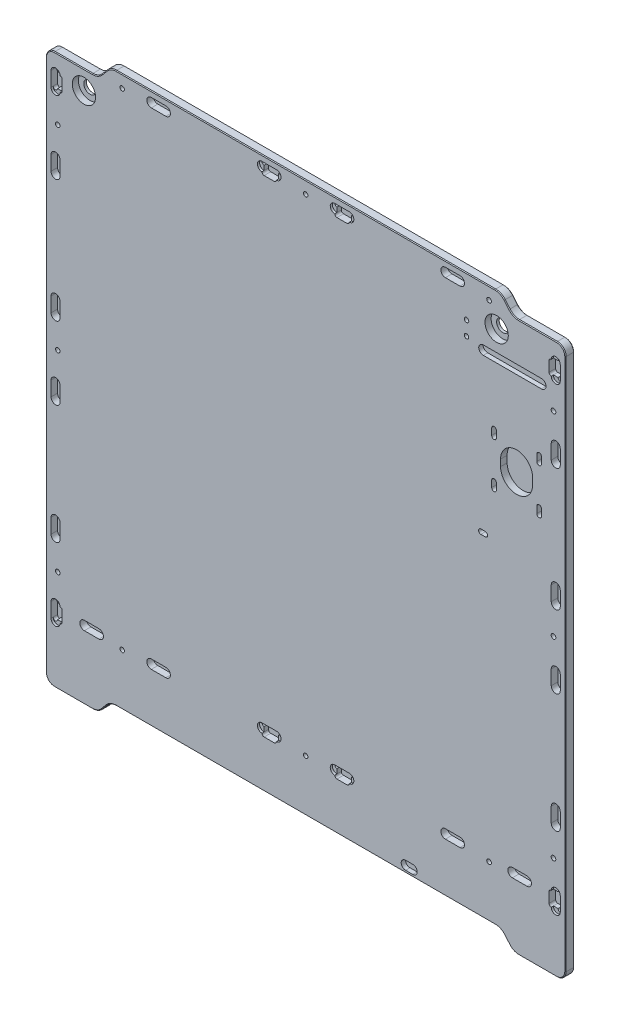
SolidWorks part; units mm, degrees
ref_plane "Alzado" through (0, 0, 0) normal (0, 0, 1) x (1, 0, 0)
ref_plane "Planta" through (0, 0, 0) normal (0, 1, 0) x (1, 0, 0)
ref_plane "Vista lateral" through (0, 0, 0) normal (1, 0, 0) x (0, 0, -1)
ref_plane "Plano1" through (0, 0, 3) normal (0, 0, 1) x (1, 0, 0)
sketch "Croquis1" plane through (0, 0, 3) normal (0, 0, 1) x (1, 0, 0)
  line L0 (178.5, -194) -> (178.5, 194)
  line L1 (178.5, 194) -> (-178.5, 194)
  line L2 (-178.5, 194) -> (-178.5, -194)
  line L3 (-178.5, -194) -> (178.5, -194)
  dimension "D1" = 357
  dimension "D2" = 388
extrude "Saliente-Extruir1" add sketch "Croquis1" against normal blind 6
sketch "Croquis2" plane through (0, 0, 3) normal (0, 0, 1) x (1, 0, 0)
  line L0 (-167.2, -144.2) -> (-168.7, -144.2)
  line L1 (-174.9, -144.2) -> (-174.9, -154.2)
  line L2 (-168.7, -154.2) -> (-167.2, -154.2)
  line L3 (-167.2, -154.2) -> (-167.2, -144.2)
  line L4 (178.5, -194) -> (178.5, 194) construction
  arc A0 (-168.7, -144.2) -> (-174.9, -144.2) centre (-171.8, -144.2) ccw
  arc A1 (-174.9, -154.2) -> (-168.7, -154.2) centre (-171.8, -154.2) ccw
  dimension "D1" = 3.1
  dimension "D2" = 345.7
extrude "Cortar-Extruir1" cut sketch "Croquis2" against normal blind 1.5
sketch "Croquis3" plane through (0, 0, 1.5) normal (0, 0, 1) x (1, 0, 0)
  line L0 (-171.9, -154.2) -> (-167.2, -154.2)
  line L1 (-167.2, -154.2) -> (-167.2, -144.2)
  line L2 (-167.2, -144.2) -> (-171.9, -144.2)
  line L3 (-174.9, -144.2) -> (-174.9, -154.2)
  line L4 (-167.2, -154.2) -> (-167.2, -144.2) construction
  arc A0 (-171.9, -144.2) -> (-174.9, -144.2) centre (-173.4, -144.2) ccw
  arc A1 (-174.9, -154.2) -> (-171.9, -154.2) centre (-173.4, -154.2) ccw
  dimension "D1" = 1.5
  dimension "D2" = 6.2
extrude "Cortar-Extruir2" cut sketch "Croquis3" against normal blind 3
sketch "Croquis4" plane through (0, 0, 3) normal (0, 0, 1) x (1, 0, 0)
  line L0 (-20, 182.4) -> (-20, 183.9)
  line L1 (-20, 190.1) -> (-30, 190.1)
  line L2 (-30, 183.9) -> (-30, 182.4)
  line L3 (-30, 182.4) -> (-20, 182.4)
  line L4 (-167.2, -154.2) -> (-167.2, -144.2) construction
  arc A0 (-20, 183.9) -> (-20, 190.1) centre (-20, 187) ccw
  arc A1 (-30, 190.1) -> (-30, 183.9) centre (-30, 187) ccw
  dimension "D1" = 3.1
  dimension "D2" = 3.1
  dimension "D3" = 137.2
extrude "Cortar-Extruir3" cut sketch "Croquis4" against normal blind 1.5
sketch "Croquis5" plane through (0, 0, 1.5) normal (0, 0, 1) x (1, 0, 0)
  line L0 (-20, 190.1) -> (-30, 190.1)
  line L1 (-30, 187.1) -> (-30, 182.4)
  line L2 (-30, 182.4) -> (-20, 182.4)
  line L3 (-20, 182.4) -> (-20, 187.1)
  arc A0 (-20, 187.1) -> (-20, 190.1) centre (-20, 188.6) ccw
  arc A1 (-30, 190.1) -> (-30, 187.1) centre (-30, 188.6) ccw
  dimension "D1" = 1.5
  dimension "D2" = 1.5
extrude "Cortar-Extruir4" cut sketch "Croquis5" against normal blind 3
sketch "Croquis6" plane through (0, 0, 3) normal (0, 0, 1) x (1, 0, 0)
  line L0 (-167.2, 171.7) -> (-168.7, 171.7)
  line L1 (-174.9, 171.7) -> (-174.9, 161.7)
  line L2 (-168.7, 161.7) -> (-167.2, 161.7)
  line L3 (-167.2, 161.7) -> (-167.2, 171.7)
  line L4 (-20, 182.4) -> (-20, 183.9) construction
  line L5 (-168.7, -154.2) -> (-167.2, -154.2) construction
  arc A0 (-168.7, 171.7) -> (-174.9, 171.7) centre (-171.8, 171.7) ccw
  arc A1 (-174.9, 161.7) -> (-168.7, 161.7) centre (-171.8, 161.7) ccw
  dimension "D1" = 3.1
  dimension "D2" = 147.2
  dimension "D3" = 151.8
  dimension "D4" = 315.9
  dimension "D5" = 325.9
extrude "Cortar-Extruir5" cut sketch "Croquis6" against normal blind 1.5
sketch "Croquis7" plane through (0, 0, 1.5) normal (0, 0, 1) x (1, 0, 0)
  line L0 (-171.9, 161.7) -> (-167.2, 161.7)
  line L1 (-167.2, 161.7) -> (-167.2, 171.7)
  line L2 (-167.2, 171.7) -> (-171.9, 171.7)
  line L3 (-174.9, 171.7) -> (-174.9, 161.7)
  line L4 (-167.2, 161.7) -> (-167.2, 171.7) construction
  arc A0 (-171.9, 171.7) -> (-174.9, 171.7) centre (-173.4, 171.7) ccw
  arc A1 (-174.9, 161.7) -> (-171.9, 161.7) centre (-173.4, 161.7) ccw
  dimension "D1" = 1.5
  dimension "D2" = 6.2
extrude "Cortar-Extruir6" cut sketch "Croquis7" against normal blind 3
sketch "Croquis8" plane through (0, 0, 3) normal (0, 0, 1) x (1, 0, 0)
  line L0 (-20, -151.6) -> (-20, -150.1)
  line L1 (-20, -143.9) -> (-30, -143.9)
  line L2 (-30, -150.1) -> (-30, -151.6)
  line L3 (-30, -151.6) -> (-20, -151.6)
  line L5 (-168.7, 161.7) -> (-167.2, 161.7) construction
  arc A0 (-20, -150.1) -> (-20, -143.9) centre (-20, -147) ccw
  arc A1 (-30, -143.9) -> (-30, -150.1) centre (-30, -147) ccw
  dimension "D1" = 3.1
  dimension "D2" = 308.7
  dimension "D3" = 313.3
extrude "Cortar-Extruir7" cut sketch "Croquis8" against normal blind 1.5
sketch "Croquis9" plane through (0, 0, 1.5) normal (0, 0, 1) x (1, 0, 0)
  line L0 (-30, -146.9) -> (-30, -151.6)
  line L1 (-30, -151.6) -> (-20, -151.6)
  line L2 (-20, -151.6) -> (-20, -146.9)
  line L3 (-20, -143.9) -> (-30, -143.9)
  line L4 (-20, -151.6) -> (-20, -150.1) construction
  arc A0 (-30, -143.9) -> (-30, -146.9) centre (-30, -145.4) ccw
  arc A1 (-20, -146.9) -> (-20, -143.9) centre (-20, -145.4) ccw
  dimension "D1" = 1.5
  dimension "D2" = 10
extrude "Cortar-Extruir8" cut sketch "Croquis9" against normal blind 3
sketch "Croquis10" plane through (0, 0, -3) normal (0, 0, -1) x (-1, 0, 0)
  line L0 (134.1086, 194) -> (134.1086, 183.9996)
  line L1 (134.1086, 183.9996) -> (178.5, 183.9996)
  line L2 (178.5, 183.9996) -> (178.5, 194)
  line L3 (178.5, 194) -> (134.1086, 194)
  line L4 (178.5, 194) -> (178.5, -194) construction
  line L5 (178.5, -194) -> (-178.5, -194) construction
  dimension "D1" = 44.3914
  dimension "D2" = 377.9996
  dimension "D3" = 388
extrude "Cortar-Extruir9" cut sketch "Croquis10" against normal through all
sketch "Croquis11" plane through (0, 0, -3) normal (0, 0, -1) x (-1, 0, 0)
  line L0 (134.1086, -194) -> (134.1086, -183.9996)
  line L1 (134.1086, -183.9996) -> (-134.1086, -183.9996)
  line L2 (-134.1086, -183.9996) -> (-134.1086, -194)
  line L3 (-134.1086, -194) -> (134.1086, -194)
  line L4 (178.5, 183.9996) -> (178.5, -194) construction
  line L5 (134.1086, 183.9996) -> (178.5, 183.9996) construction
  dimension "D1" = 44.3914
  dimension "D2" = 312.6086
  dimension "D3" = 367.9992
  dimension "D4" = 377.9996
extrude "Cortar-Extruir10" cut sketch "Croquis11" against normal through all
sketch "Croquis12" plane through (0, 0, 3) normal (0, 0, 1) x (1, 0, 0)
  line L0 (162, 74.95) -> (162, 79.45)
  line L1 (158.8, 79.45) -> (158.8, 74.95)
  line L2 (-178.5, 183.9996) -> (-178.5, -194) construction
  line L3 (-178.5, -194) -> (-134.1086, -194) construction
  arc A0 (162, 79.45) -> (158.8, 79.45) centre (160.4, 79.45) ccw
  arc A1 (158.8, 74.95) -> (162, 74.95) centre (160.4, 74.95) ccw
  dimension "D1" = 1.6
  dimension "D2" = 338.9
  dimension "D3" = 268.95
  dimension "D4" = 273.45
extrude "Cortar-Extruir11" cut sketch "Croquis12" against normal through all
sketch "Croquis13" plane through (0, 0, 3) normal (0, 0, 1) x (1, 0, 0)
  line L0 (158.8, 110.45) -> (158.8, 105.95)
  line L1 (162, 105.95) -> (162, 110.45)
  line L2 (-178.5, 183.9996) -> (-178.5, -194) construction
  line L3 (-178.5, -194) -> (-134.1086, -194) construction
  arc A0 (158.8, 105.95) -> (162, 105.95) centre (160.4, 105.95) ccw
  arc A1 (162, 110.45) -> (158.8, 110.45) centre (160.4, 110.45) ccw
  dimension "D1" = 1.6
  dimension "D2" = 338.9
  dimension "D3" = 299.95
  dimension "D4" = 304.45
extrude "Cortar-Extruir12" cut sketch "Croquis13" against normal through all
sketch "Croquis14" plane through (0, 0, 3) normal (0, 0, 1) x (1, 0, 0)
  line L0 (127.8, 79.45) -> (127.8, 74.95)
  line L1 (131, 74.95) -> (131, 79.45)
  line L2 (-178.5, 183.9996) -> (-178.5, -194) construction
  line L3 (-178.5, -194) -> (-134.1086, -194) construction
  arc A0 (131, 79.45) -> (127.8, 79.45) centre (129.4, 79.45) ccw
  arc A1 (127.8, 74.95) -> (131, 74.95) centre (129.4, 74.95) ccw
  dimension "D1" = 1.6
  dimension "D2" = 307.9
  dimension "D3" = 268.95
  dimension "D4" = 273.45
extrude "Cortar-Extruir13" cut sketch "Croquis14" against normal through all
sketch "Croquis15" plane through (0, 0, 3) normal (0, 0, 1) x (1, 0, 0)
  line L0 (127.8, 110.45) -> (127.8, 105.95)
  line L1 (131, 105.95) -> (131, 110.45)
  line L2 (-178.5, 183.9996) -> (-178.5, -194) construction
  line L3 (-178.5, -194) -> (-134.1086, -194) construction
  arc A0 (131, 110.45) -> (127.8, 110.45) centre (129.4, 110.45) ccw
  arc A1 (127.8, 105.95) -> (131, 105.95) centre (129.4, 105.95) ccw
  dimension "D1" = 1.6
  dimension "D2" = 307.9
  dimension "D3" = 299.95
  dimension "D4" = 304.45
extrude "Cortar-Extruir14" cut sketch "Croquis15" against normal through all
sketch "Croquis16" plane through (0, 0, -3) normal (0, 0, -1) x (-1, 0, 0)
  line L0 (-123.4, 43.4) -> (-120.4, 43.4)
  line L1 (-120.4, 46.6) -> (-123.4, 46.6)
  line L2 (-127.8, 79.45) -> (-127.8, 74.95) construction
  arc A0 (-120.4, 43.4) -> (-120.4, 46.6) centre (-120.4, 45) ccw
  arc A1 (-123.4, 46.6) -> (-123.4, 43.4) centre (-123.4, 45) ccw
  dimension "D1" = 1.6
  dimension "D2" = 4.4
  dimension "D3" = 7.4
  dimension "D4" = 29.95
extrude "Cortar-Extruir15" cut sketch "Croquis16" against normal through all
sketch "Croquis17" plane through (0, 0, 3) normal (0, 0, 1) x (1, 0, 0)
  line L0 (73.65, -176.3) -> (68.65, -176.3)
  line L1 (68.65, -182.3) -> (73.65, -182.3)
  line L2 (178.5, -194) -> (178.5, 194) construction
  line L3 (134.1086, -194) -> (178.5, -194) construction
  arc A0 (68.65, -176.3) -> (68.65, -182.3) centre (68.65, -179.3) ccw
  arc A1 (73.65, -182.3) -> (73.65, -176.3) centre (73.65, -179.3) ccw
  dimension "D1" = 3
  dimension "D2" = 104.85
  dimension "D3" = 109.85
  dimension "D4" = 14.7
extrude "Cortar-Extruir16" cut sketch "Croquis17" against normal blind 3
sketch "Croquis18" plane through (0, 0, 3) normal (0, 0, 1) x (1, 0, 0)
  line L0 (122, 150.7237) -> (162, 150.7237)
  line L1 (162, 156.9237) -> (122, 156.9237)
  line L2 (-134.1086, 183.9996) -> (-134.1086, 194) construction
  line L3 (178.5, 194) -> (-134.1086, 194) construction
  arc A0 (162, 150.7237) -> (162, 156.9237) centre (162, 153.8237) ccw
  arc A1 (122, 156.9237) -> (122, 150.7237) centre (122, 153.8237) ccw
  dimension "D1" = 3.1
  dimension "D2" = 256.1086
  dimension "D3" = 296.1086
  dimension "D4" = 40.1763
extrude "Cortar-Extruir17" cut sketch "Croquis18" against normal blind 3
sketch "Croquis19" plane through (0, 0, 3) normal (0, 0, 1) x (1, 0, 0)
  line L0 (-152, -150.1) -> (-142, -150.1)
  line L1 (-142, -143.9) -> (-152, -143.9)
  line L2 (178.5, -194) -> (178.5, 194) construction
  line L3 (134.1086, -194) -> (178.5, -194) construction
  arc A0 (-142, -150.1) -> (-142, -143.9) centre (-142, -147) ccw
  arc A1 (-152, -143.9) -> (-152, -150.1) centre (-152, -147) ccw
  dimension "D1" = 3.1
  dimension "D2" = 320.5
  dimension "D3" = 330.5
  dimension "D4" = 47
extrude "Cortar-Extruir18" cut sketch "Croquis19" against normal blind 4.5
sketch "Croquis20" plane through (0, 0, 3) normal (0, 0, 1) x (1, 0, 0)
  line L0 (-106, -150.1) -> (-96, -150.1)
  line L1 (-96, -143.9) -> (-106, -143.9)
  line L2 (162, 105.95) -> (162, 110.45) construction
  line L3 (162, 156.9237) -> (122, 156.9237) construction
  arc A0 (-96, -150.1) -> (-96, -143.9) centre (-96, -147) ccw
  arc A1 (-106, -143.9) -> (-106, -150.1) centre (-106, -147) ccw
  dimension "D1" = 3.1
  dimension "D2" = 258
  dimension "D3" = 268
  dimension "D4" = 303.9237
extrude "Cortar-Extruir19" cut sketch "Croquis20" against normal blind 4.5
sketch "Croquis21" plane through (0, 0, 3) normal (0, 0, 1) x (1, 0, 0)
  line L0 (-168.7, -104.2) -> (-168.7, -94.2)
  line L1 (-174.9, -94.2) -> (-174.9, -104.2)
  line L2 (162, 105.95) -> (162, 110.45) construction
  line L3 (68.65, -182.3) -> (73.65, -182.3) construction
  arc A0 (-174.9, -104.2) -> (-168.7, -104.2) centre (-171.8, -104.2) ccw
  arc A1 (-168.7, -94.2) -> (-174.9, -94.2) centre (-171.8, -94.2) ccw
  dimension "D1" = 3.1
  dimension "D2" = 333.8
  dimension "D3" = 78.1
  dimension "D4" = 88.1
extrude "Cortar-Extruir20" cut sketch "Croquis21" against normal blind 4.5
sketch "Croquis22" plane through (0, 0, 3) normal (0, 0, 1) x (1, 0, 0)
  line L0 (-168.7, -22.5) -> (-168.7, -12.5)
  line L1 (-174.9, -12.5) -> (-174.9, -22.5)
  line L2 (-174.9, -94.2) -> (-174.9, -104.2) construction
  line L3 (68.65, -182.3) -> (73.65, -182.3) construction
  arc A0 (-174.9, -22.5) -> (-168.7, -22.5) centre (-171.8, -22.5) ccw
  arc A1 (-168.7, -12.5) -> (-174.9, -12.5) centre (-171.8, -12.5) ccw
  dimension "D1" = 3.1
  dimension "D2" = 3.1
  dimension "D3" = 159.8
  dimension "D4" = 169.8
extrude "Cortar-Extruir21" cut sketch "Croquis22" against normal blind 4.5
sketch "Croquis23" plane through (0, 0, 3) normal (0, 0, 1) x (1, 0, 0)
  line L0 (-168.7, 27.5) -> (-168.7, 37.5)
  line L1 (-174.9, 37.5) -> (-174.9, 27.5)
  line L2 (-174.9, -94.2) -> (-174.9, -104.2) construction
  line L3 (68.65, -182.3) -> (73.65, -182.3) construction
  arc A0 (-174.9, 27.5) -> (-168.7, 27.5) centre (-171.8, 27.5) ccw
  arc A1 (-168.7, 37.5) -> (-174.9, 37.5) centre (-171.8, 37.5) ccw
  dimension "D1" = 3.1
  dimension "D2" = 3.1
  dimension "D3" = 209.8
  dimension "D4" = 219.8
extrude "Cortar-Extruir22" cut sketch "Croquis23" against normal blind 4.5
sketch "Croquis24" plane through (0, 0, 3) normal (0, 0, 1) x (1, 0, 0)
  line L0 (-168.7, 111.7) -> (-168.7, 121.7)
  line L1 (-174.9, 121.7) -> (-174.9, 111.7)
  line L2 (-174.9, -94.2) -> (-174.9, -104.2) construction
  line L3 (68.65, -182.3) -> (73.65, -182.3) construction
  arc A0 (-174.9, 111.7) -> (-168.7, 111.7) centre (-171.8, 111.7) ccw
  arc A1 (-168.7, 121.7) -> (-174.9, 121.7) centre (-171.8, 121.7) ccw
  dimension "D1" = 3.1
  dimension "D2" = 3.1
  dimension "D3" = 294
  dimension "D4" = 304
extrude "Cortar-Extruir23" cut sketch "Croquis24" against normal blind 4.5
sketch "Croquis25" plane through (0, 0, 3) normal (0, 0, 1) x (1, 0, 0)
  line L0 (-106, 183.9) -> (-96, 183.9)
  line L1 (-96, 190.1) -> (-106, 190.1)
  line L2 (-174.9, -94.2) -> (-174.9, -104.2) construction
  line L3 (68.65, -182.3) -> (73.65, -182.3) construction
  arc A0 (-96, 183.9) -> (-96, 190.1) centre (-96, 187) ccw
  arc A1 (-106, 190.1) -> (-106, 183.9) centre (-106, 187) ccw
  dimension "D1" = 3.1
  dimension "D2" = 68.9
  dimension "D3" = 78.9
  dimension "D4" = 369.3
extrude "Cortar-Extruir24" cut sketch "Croquis25" against normal blind 4.5
mirror "Simetría1" about plane through (0, 0, 0) normal (1, 0, 0) of "Cortar-Extruir22", "Cortar-Extruir1", "Cortar-Extruir2", "Cortar-Extruir3", "Cortar-Extruir4", "Cortar-Extruir5", "Cortar-Extruir6", "Cortar-Extruir7", "Cortar-Extruir8", "Cortar-Extruir9", "Cortar-Extruir18", "Cortar-Extruir19", "Cortar-Extruir20", "Cortar-Extruir21", "Cortar-Extruir23", "Cortar-Extruir24"
sketch "Croquis27" plane through (0, 0, 3) normal (0, 0, 1) x (1, 0, 0)
  line L0 (155.9, 90.45) -> (155.9, 94.95)
  line L1 (133.9, 94.95) -> (133.9, 90.45)
  line L2 (-174.9, -94.2) -> (-174.9, -104.2) construction
  line L3 (68.65, -182.3) -> (73.65, -182.3) construction
  arc A0 (155.9, 94.95) -> (133.9, 94.95) centre (144.9, 94.95) ccw
  arc A1 (133.9, 90.45) -> (155.9, 90.45) centre (144.9, 90.45) ccw
  dimension "D1" = 11
  dimension "D2" = 319.8
  dimension "D3" = 272.75
  dimension "D4" = 277.25
extrude "Cortar-Extruir25" cut sketch "Croquis27" against normal blind 4.5
draft "Ángulo de salida1" type of draft neutral plane draft angle 40 faces to draft 2 face at (-134.1086, -188.9998, 0) face at (134.1086, -188.9998, 0) neutral plane through (-134.1086, -183.9996, 3) neutral plane normal (0, -1, 0) parameters "D1"=40
draft "Ángulo de salida2" type of draft neutral plane draft angle 40 faces to draft 2 face at (-134.1086, 188.9998, 0) face at (134.1086, 188.9998, 0) neutral plane through (178.5, 194, -3) neutral plane normal (0, 1, 0) parameters "D1"=40
hole_wizard "Diámetro de taladro Ø3.2 (3.2)1" positions "Croquis29" profile "Croquis28" hole size "Ø3.2" standard "Ansi Metric"
sketch "Croquis29" plane through (0, 0, 3) normal (0, 0, 1) x (1, 0, 0)
  point P0 (170.25, -124.3)
  point P1 (170.25, 7.6)
  point P2 (170.25, 141.7)
  point P3 (126, 185.45)
  point P4 (126, -148.55)
sketch "Croquis28" plane through (170.25, -124.3, 3) normal (1, 0, 0) x (0, -1, 0)
  line L0 (0, 0) -> (0, 6)
  line L1 (0, 6) -> (1.6, 6)
  line L2 (1.6, 6) -> (1.6, 0)
  line L5 (1.6, 0) -> (0, 0)
  line L11 (0, -6.35) -> (0, 107.95) construction
  dimension "Diámetro de taladro hasta el siguiente" = 3.2
  dimension "Profundidad de taladro hasta el siguiente" = 6
hole_wizard "Diámetro de taladro Ø3.1 (3.1)1" positions "Croquis31" profile "Croquis30" hole size "Ø3.1" standard "Ansi Metric"
sketch "Croquis31" plane through (0, 0, -3) normal (0, 0, -1) x (-1, 0, 0)
  point P0 (-110.5, 156.3)
  point P1 (-110.5, 166)
  point P2 (0, 185.45)
  point P3 (0, -148.55)
  point P4 (170.25, -124.3)
  point P5 (170.25, 7.6)
  point P6 (170.25, 141.7)
  point P7 (126, 185.45)
  point P8 (126, -148.55)
sketch "Croquis30" plane through (110.5, 156.3, -3) normal (1, 0, 0) x (0, 1, 0)
  line L0 (0, 0) -> (0, 6)
  line L1 (0, 6) -> (1.55, 6)
  line L2 (1.55, 6) -> (1.55, 0)
  line L5 (1.55, 0) -> (0, 0)
  line L11 (0, -6.35) -> (0, 107.95) construction
  dimension "Diámetro de taladro hasta el siguiente" = 3.1
  dimension "Profundidad de taladro hasta el siguiente" = 6
hole_wizard "Refrentado para perno con cabeza hexagonal de M81" positions "Croquis33" profile "Croquis32" counterbore size "M8" standard "Ansi Metric"
sketch "Croquis33" plane through (0, 0, 3) normal (0, 0, 1) x (1, 0, 0)
  point P0 (-152.3, 171)
  point P1 (131.2, 171)
sketch "Croquis32" plane through (-152.3, 171, 3) normal (1, 0, 0) x (0, -1, 0)
  line L0 (0, 0) -> (0, 6)
  line L1 (0, 6) -> (4.25, 6)
  line L3 (4.25, 6) -> (4.25, 4.2)
  line L4 (4.25, 4.2) -> (8, 4.2)
  line L5 (8, 4.2) -> (8, 0)
  line L7 (8, 0) -> (0, 0)
  line L11 (0, -6.35) -> (0, 107.95) construction
  dimension "Diámetro de taladro hasta el siguiente" = 8.5
  dimension "Profundidad de taladro hasta el siguiente" = 6
  dimension "Diámetro de refrentado" = 16
  dimension "Profundidad de refrentado" = 4.2
fillet "Redondeo1" radius 6 4 edges at (178.5, -194, 0) (178.5, 183.9996, 0) (-178.5, -194, 0) (-178.5, 183.9996, 0) tangent propagation no
fillet "Redondeo2" radius 8.5 8 edges at (-142.5, -194, 0) (134.1086, -183.9996, 0) (142.5, -194, 0) (-142.5, 183.9996, 0) (-134.1086, -183.9996, 0) (134.1086, 194, 0) (142.5, 183.9996, 0) (-134.1086, 194, 0) tangent propagation no
chamfer "Chaflán1" distance 0.5 angle 45 48 edges at (-176.7426, -192.2426, -3) (-159.4818, -194, -3) (-178.5, -5.0002, -3) (-142.8714, -193.2036, -3) (-176.7426, 182.2422, -3) (-138.3043, -188.9998, -3) (-159.4818, 183.9996, -3) (-133.7373, -184.796, -3) (-142.8714, 184.796, -3) (0, -183.9996, -3) (-138.3043, 188.9998, -3) (133.7373, -184.796, -3) (-133.7373, 193.2036, -3) (138.3043, -188.9998, -3) (0, 194, -3) (142.8714, -193.2036, -3) (133.7373, 193.2036, -3) (159.4818, -194, -3) (138.3043, 188.9998, -3) (176.7426, -192.2426, -3) (142.8714, 184.796, -3) (178.5, -5.0002, -3) (159.4818, 183.9996, -3) (176.7426, 182.2422, -3) (159.4818, -194, 3) (142.8714, -193.2036, 3) (176.7426, -192.2426, 3) (138.3043, -188.9998, 3) (178.5, -5.0002, 3) (133.7373, -184.796, 3) (176.7426, 182.2422, 3) (0, -183.9996, 3) (159.4818, 183.9996, 3) (-133.7373, -184.796, 3) (142.8714, 184.796, 3) (-138.3043, -188.9998, 3) (138.3043, 188.9998, 3) (-142.8714, -193.2036, 3) (133.7373, 193.2036, 3) (-159.4818, -194, 3) (0, 194, 3) (-176.7426, -192.2426, 3) (-133.7373, 193.2036, 3) (-178.5, -5.0002, 3) (-138.3043, 188.9998, 3) (-176.7426, 182.2422, 3) (-142.8714, 184.796, 3) (-159.4818, 183.9996, 3)
fillet "Redondeo3" radius 1.5 16 edges at (-30, -151.6, 0.75) (-167.2, -154.2, 0.75) (20, 182.4, 0.75) (-20, -151.6, 0.75) (-167.2, 161.7, 0.75) (-20, 182.4, 0.75) (30, -151.6, 0.75) (167.2, -144.2, 0.75) (30, 182.4, 0.75) (167.2, -154.2, 0.75) (-167.2, -144.2, 0.75) (167.2, 171.7, 0.75) (-167.2, 171.7, 0.75) (167.2, 161.7, 0.75) (20, -151.6, 0.75) (-30, 182.4, 0.75) tangent propagation no
